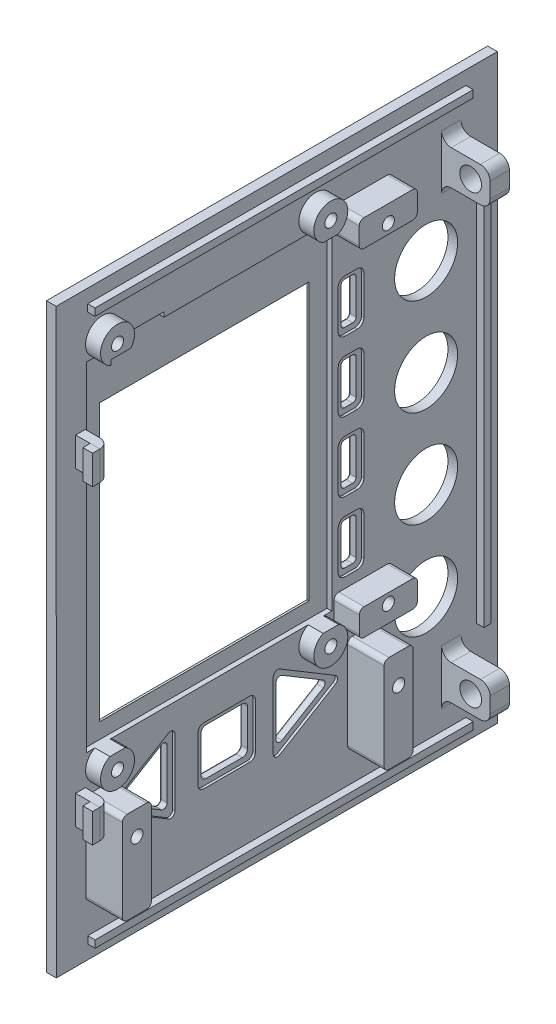
SolidWorks part; units mm, degrees
ref_plane "Front Plane" through (0, 0, 0) normal (0, 0, 1) x (1, 0, 0)
ref_plane "Top Plane" through (0, 0, 0) normal (0, 1, 0) x (1, 0, 0)
ref_plane "Right Plane" through (0, 0, 0) normal (1, 0, 0) x (0, 0, -1)
ref_plane "Plane2" through (-1175.048, -0.0877, 0) normal (-1, -0.0001, 0) x (0, 0, 1)
sketch "Sketch2" plane through (-1175.048, -0.0877, 0) normal (-1, -0.0001, 0) x (0, 0, 1)
  line L0 (-1289.195, -889.282) -> (-1289.195, -789.282) construction
  line L1 (-1204.195, -779.282) -> (-1295.195, -779.282)
  line L2 (-1204.195, -779.282) -> (-1204.195, -899.282)
  line L3 (-1204.195, -899.282) -> (-1295.195, -899.282)
  line L4 (-1295.195, -779.282) -> (-1295.195, -899.282)
  line L5 (-1289.195, -889.282) -> (-1287.685, -889.282) construction
  line L6 (-1289.195, -789.282) -> (-1287.685, -789.282) construction
  circle A0 centre (-1280.5, -869.282) radius 6.5
  circle A1 centre (-1280.5, -849.282) radius 6.5
  circle A2 centre (-1280.5, -829.282) radius 6.5
  circle A3 centre (-1280.5, -809.282) radius 6.5
  ellipse E0 centre (-1280.5, -869.282) end of major axis (-1280.4976, -868.632) minor radius 0.65 construction
  ellipse E1 centre (-1280.5, -849.282) end of major axis (-1280.4976, -848.632) minor radius 0.65 construction
  ellipse E2 centre (-1280.5, -829.282) end of major axis (-1280.4976, -828.632) minor radius 0.65 construction
  ellipse E3 centre (-1280.5, -809.282) end of major axis (-1280.4976, -808.632) minor radius 0.65 construction
  ellipse E4 centre (-1280.5, -869.282) end of major axis (-1280.4976, -868.632) minor radius 0.65
  ellipse E5 centre (-1280.5, -849.282) end of major axis (-1280.4976, -848.632) minor radius 0.65 construction
  ellipse E6 centre (-1280.5, -829.282) end of major axis (-1280.4976, -828.632) minor radius 0.65
  ellipse E7 centre (-1280.5, -809.282) end of major axis (-1280.4976, -808.632) minor radius 0.65
  dimension "D5" = 13
  dimension "D6" = 13
  dimension "D7" = 13
  dimension "D8" = 13
  dimension "D1" = 6
  dimension "D2" = 10
  dimension "D3" = 10
  dimension "D4" = 91
extrude "Boss-Extrude2" add sketch "Sketch2" along normal blind 2 contours L1 L4 L3 L2 A3 A2 A1 A0 region at (-1174.9854, -839.3697, -1248.1207)
sketch "Sketch3" plane through (-1177.048, -0.0879, 0) normal (-1, -0.0001, 0) x (0, 0, 1)
  line L12 (-1214.15, -858.982) -> (-1257.35, -858.982) construction
  line L13 (-1257.35, -858.982) -> (-1257.35, -802.002) construction
  line L14 (-1214.15, -802.002) -> (-1214.15, -858.982) construction
  line L15 (-1257.35, -802.002) -> (-1214.15, -802.002) construction
  line L16 (-1214.15, -858.982) -> (-1257.35, -858.982)
  line L17 (-1257.35, -858.982) -> (-1257.35, -802.002)
  line L18 (-1214.15, -802.002) -> (-1214.15, -858.982)
  line L19 (-1257.35, -802.002) -> (-1214.15, -802.002)
extrude "tft_cutout" cut sketch "Sketch3" against normal through all
sketch "tft_inset_cutout" plane through (-1175.048, -0.0877, 0) normal (1, 0.0001, 0) x (0, 0, -1)
  line L4 (1210.95, -792.861) -> (1210.95, -861.661) construction
  line L5 (1260.55, -792.861) -> (1210.95, -792.861) construction
  line L12 (1260.55, -861.661) -> (1260.55, -792.861) construction
  line L17 (1210.95, -861.661) -> (1260.55, -861.661) construction
  line L18 (1260.55, -861.661) -> (1260.55, -792.861) construction
  line L19 (1210.95, -861.661) -> (1260.55, -861.661) construction
  line L20 (1210.95, -792.861) -> (1210.95, -861.661) construction
  line L21 (1260.55, -792.861) -> (1210.95, -792.861) construction
  line L22 (1261.05, -792.361) -> (1210.45, -792.361)
  line L26 (1212.45, -792.861) -> (1226.45, -792.861)
  line L27 (1212.45, -792.861) -> (1212.45, -791.361)
  line L28 (1212.45, -791.361) -> (1226.45, -791.361)
  line L29 (1226.45, -792.861) -> (1226.45, -791.361)
  line L30 (1210.45, -792.361) -> (1210.45, -862.161)
  line L31 (1210.45, -862.161) -> (1261.05, -862.161)
  line L32 (1261.05, -862.161) -> (1261.05, -792.361)
  line M40 (1257.35, -858.982) -> (1214.15, -858.982)
  line M41 (1214.15, -858.982) -> (1214.15, -802.002)
  line M42 (1214.15, -802.002) -> (1257.35, -802.002)
  line M43 (1257.35, -802.002) -> (1257.35, -858.982)
  dimension "D3" = 1.5
  dimension "D4" = 0.5
  dimension "D1" = 14
  dimension "D2" = 1.5
extrude "Cut-Extrude2" cut sketch "tft_inset_cutout" against normal up to surface (1 mm away) contours L18 | L31 L32 L22 L29 L26 L27 L30 M43 M40 M41 M42 | L26 L29 L22 L27 | L22 L29 L28 L27 region at (-1174.9863, -827.3487, -1260.1879) region at (-1174.9889, -792.6987, -1219.45) region at (-1174.9889, -791.9487, -1219.45)
chamfer "Chamfer2" distance 1 angle 30 4 edges at (-1176.986, -830.5798, -1257.35) (-1176.9839, -859.0698, -1235.75) (-1176.986, -830.5798, -1214.15) (-1176.9882, -802.0898, -1235.75) first distance on face at (-1176.986, -830.5798, -1235.75)
sketch "Sketch6" plane through (-1175.048, -0.0877, 0) normal (1, 0.0001, 0) x (0, 0, -1)
  line L5 (1261.5, -864.9905) -> (1273.5, -864.9905)
  line L6 (1261.5, -864.9905) -> (1261.5, -859.4905)
  line L7 (1261.5, -859.4905) -> (1273.5, -859.4905)
  line L8 (1261.5, -864.9905) -> (1273.5, -864.9905)
  line L9 (1273.5, -864.9905) -> (1273.5, -789.9905)
  line L10 (1273.5, -789.9905) -> (1261.5, -789.9905)
  line L11 (1261.5, -789.9905) -> (1261.5, -864.9905)
  line L12 (1261.5, -864.9905) -> (1273.5, -864.9905) construction
  line L13 (1273.5, -864.9905) -> (1273.5, -789.9905) construction
  line L14 (1273.5, -789.9905) -> (1261.5, -789.9905) construction
  line L15 (1261.5, -789.9905) -> (1261.5, -864.9905) construction
  line L16 (1273.5, -864.9905) -> (1273.5, -859.4905)
  line L17 (1261.5, -789.9905) -> (1273.5, -789.9905)
  line L18 (1261.5, -789.9905) -> (1261.5, -795.4905)
  line L19 (1261.5, -795.4905) -> (1273.5, -795.4905)
  line L20 (1273.5, -789.9905) -> (1273.5, -795.4905)
  circle A0 centre (1267.5, -861.4905) radius 1.25 construction
  circle A1 centre (1267.5, -861.4905) radius 1.25 construction
  circle A2 centre (1267.5, -861.4905) radius 1.25
  circle A3 centre (1267.5, -793.4905) radius 1.25 construction
  circle A4 centre (1267.5, -793.4905) radius 1.25 construction
  circle A5 centre (1267.5, -793.4905) radius 1.25
  dimension "D2" = 2.5
  dimension "D4" = 2.5
  dimension "D3" = 2
  dimension "D5" = 2
extrude "menu_standoffs" add sketch "Sketch6" along normal up to surface (5.203 mm away)
fillet "Fillet1" radius 1 8 edges at (-1172.3871, -795.578, -1261.5) (-1172.3871, -795.578, -1273.5) (-1172.3875, -790.078, -1273.5) (-1172.3875, -790.078, -1261.5) (-1172.3824, -859.578, -1273.5) (-1172.3824, -859.578, -1261.5) (-1172.382, -865.078, -1261.5) (-1172.382, -865.078, -1273.5)
sketch "Sketch7" plane through (-1169.845, -0.0873, 0) normal (1, 0.0001, 0) x (0, 0, -1)
  circle A0 centre (1267.5, -861.4905) radius 1.25 construction
  circle A1 centre (1267.5, -793.4905) radius 1.25 construction
  circle A2 centre (1267.5, -861.4905) radius 1.25
  circle A3 centre (1267.5, -793.4905) radius 1.25
extrude "menu_standoff_holes" [suppressed] cut sketch "Sketch7" against normal blind 5 contours A2
sketch "Sketch8" plane through (-1175.048, -0.0877, 0) normal (1, 0.0001, 0) x (0, 0, -1)
  circle A0 centre (1213.75, -865.282) radius 1.55 construction
  circle A1 centre (1257.75, -865.282) radius 1.55 construction
  circle A2 centre (1257.75, -789.202) radius 1.55 construction
  circle A3 centre (1213.75, -789.2023) radius 1.55 construction
  circle A4 centre (1213.75, -865.282) radius 1.55 construction
  circle A5 centre (1257.75, -865.282) radius 1.55 construction
  circle A6 centre (1257.75, -789.202) radius 1.55 construction
  circle A7 centre (1213.75, -789.2023) radius 1.55 construction
  circle A8 centre (1213.75, -789.2023) radius 3.5
  circle A9 centre (1257.75, -789.202) radius 3.5
  circle A10 centre (1257.75, -865.282) radius 3.5
  circle A11 centre (1213.75, -865.282) radius 3.5
  circle A12 centre (1213.75, -789.2023) radius 1.25
  circle A13 centre (1213.75, -865.282) radius 1.25
  circle A14 centre (1257.75, -865.282) radius 1.25
  circle A15 centre (1257.75, -789.202) radius 1.25
  dimension "D2" = 2.5
  dimension "D1" = 7
extrude "TFT_standoffs" add sketch "Sketch8" along normal up to surface (3.09 mm away)
sketch "Sketch9" plane through (-1175.048, -0.0877, 0) normal (1, 0.0001, 0) x (0, 0, -1)
  circle A0 centre (1213.75, -789.2023) radius 1.25 construction
  circle A1 centre (1213.75, -865.282) radius 1.25 construction
  circle A2 centre (1257.75, -865.282) radius 1.25 construction
  circle A3 centre (1257.75, -789.202) radius 1.25 construction
  circle A4 centre (1213.75, -789.2023) radius 1.25
  circle A5 centre (1213.75, -865.282) radius 1.25
  circle A6 centre (1257.75, -865.282) radius 1.25
  circle A7 centre (1257.75, -789.202) radius 1.25
extrude "TFT_standoff_holes" cut sketch "Sketch9" against normal offset from surface (1 mm away) 1 up to face at (-1176.986, -830.5798, -1235.75)
extrude "Cut-Extrude5" cut sketch "Sketch5<3>" along normal through all contours L31 L32 L22 L29 L26 L27 L30 M43 M40 M41 M42 | L22 L29 L28 L27 | L26 L29 L22 L27 region at (-1174.9863, -827.3487, -1260.1879) region at (-1174.9889, -792.6987, -1219.45) region at (-1174.9889, -791.9487, -1219.45)
sketch "Sketch5<3>" plane through (-1175.048, -0.0877, 0) normal (1, 0.0001, 0) x (0, 0, -1) same geometry as "tft_inset_cutout"
sketch "Sketch10" plane through (-1175.048, -0.0877, 0) normal (1, 0.0001, 0) x (0, 0, -1)
  line L0 (1267.2535, -804.997) -> (1267.2535, -812.997) construction
  line L1 (1266.2535, -813.997) -> (1263.7535, -813.997) construction
  line L2 (1262.7535, -812.997) -> (1262.7535, -804.997) construction
  line L3 (1263.7535, -803.997) -> (1266.2535, -803.997) construction
  line L4 (1267.2535, -804.997) -> (1267.2535, -812.997) construction
  line L5 (1266.2535, -813.997) -> (1263.7535, -813.997) construction
  line L6 (1262.7535, -812.997) -> (1262.7535, -804.997) construction
  line L7 (1263.7535, -803.997) -> (1266.2535, -803.997) construction
  line L8 (1267.6535, -804.997) -> (1267.6535, -812.997)
  line L9 (1266.2535, -814.397) -> (1263.7535, -814.397)
  line L10 (1262.3535, -812.997) -> (1262.3535, -804.997)
  line L11 (1263.7535, -803.597) -> (1266.2535, -803.597)
  line L12 (1267.6535, -819.327) -> (1267.6535, -827.327)
  line L13 (1266.2535, -828.727) -> (1263.7535, -828.727)
  line L14 (1262.3535, -827.327) -> (1262.3535, -819.327)
  line L15 (1263.7535, -817.927) -> (1266.2535, -817.927)
  line L16 (1267.2535, -819.327) -> (1267.2535, -827.327) construction
  line L17 (1266.2535, -828.327) -> (1263.7535, -828.327) construction
  line L18 (1262.7535, -827.327) -> (1262.7535, -819.327) construction
  line L19 (1263.7535, -818.327) -> (1266.2535, -818.327) construction
  line L20 (1267.6535, -833.657) -> (1267.6535, -841.657)
  line L21 (1266.2535, -843.057) -> (1263.7535, -843.057)
  line L22 (1262.3535, -841.657) -> (1262.3535, -833.657)
  line L23 (1263.7535, -832.257) -> (1266.2535, -832.257)
  line L24 (1267.2535, -833.657) -> (1267.2535, -841.657) construction
  line L25 (1266.2535, -842.657) -> (1263.7535, -842.657) construction
  line L26 (1262.7535, -841.657) -> (1262.7535, -833.657) construction
  line L27 (1263.7535, -832.657) -> (1266.2535, -832.657) construction
  line L28 (1267.6535, -847.987) -> (1267.6535, -855.987)
  line L29 (1266.2535, -857.387) -> (1263.7535, -857.387)
  line L30 (1262.3535, -855.987) -> (1262.3535, -847.987)
  line L31 (1263.7535, -846.587) -> (1266.2535, -846.587)
  line L32 (1267.2535, -847.987) -> (1267.2535, -855.987) construction
  line L33 (1266.2535, -856.987) -> (1263.7535, -856.987) construction
  line L34 (1262.7535, -855.987) -> (1262.7535, -847.987) construction
  line L35 (1263.7535, -846.987) -> (1266.2535, -846.987) construction
  arc A0 (1267.2535, -804.997) -> (1266.2535, -803.997) centre (1266.2535, -804.997) ccw construction
  arc A1 (1266.2535, -813.997) -> (1267.2535, -812.997) centre (1266.2535, -812.997) ccw construction
  arc A2 (1262.7535, -812.997) -> (1263.7535, -813.997) centre (1263.7535, -812.997) ccw construction
  arc A3 (1263.7535, -803.997) -> (1262.7535, -804.997) centre (1263.7535, -804.997) ccw construction
  arc A4 (1267.2535, -804.997) -> (1266.2535, -803.997) centre (1266.2535, -804.997) ccw construction
  arc A5 (1266.2535, -813.997) -> (1267.2535, -812.997) centre (1266.2535, -812.997) ccw construction
  arc A6 (1262.7535, -812.997) -> (1263.7535, -813.997) centre (1263.7535, -812.997) ccw construction
  arc A7 (1263.7535, -803.997) -> (1262.7535, -804.997) centre (1263.7535, -804.997) ccw construction
  arc A8 (1266.2535, -814.397) -> (1267.6535, -812.997) centre (1266.2535, -812.997) ccw
  arc A9 (1262.3535, -812.997) -> (1263.7535, -814.397) centre (1263.7535, -812.997) ccw
  arc A10 (1263.7535, -803.597) -> (1262.3535, -804.997) centre (1263.7535, -804.997) ccw
  arc A11 (1267.6535, -804.997) -> (1266.2535, -803.597) centre (1266.2535, -804.997) ccw
  arc A12 (1266.2535, -828.727) -> (1267.6535, -827.327) centre (1266.2535, -827.327) ccw
  arc A13 (1262.3535, -827.327) -> (1263.7535, -828.727) centre (1263.7535, -827.327) ccw
  arc A14 (1263.7535, -817.927) -> (1262.3535, -819.327) centre (1263.7535, -819.327) ccw
  arc A15 (1267.6535, -819.327) -> (1266.2535, -817.927) centre (1266.2535, -819.327) ccw
  arc A16 (1267.2535, -819.327) -> (1266.2535, -818.327) centre (1266.2535, -819.327) ccw construction
  arc A17 (1266.2535, -828.327) -> (1267.2535, -827.327) centre (1266.2535, -827.327) ccw construction
  arc A18 (1262.7535, -827.327) -> (1263.7535, -828.327) centre (1263.7535, -827.327) ccw construction
  arc A19 (1263.7535, -818.327) -> (1262.7535, -819.327) centre (1263.7535, -819.327) ccw construction
  arc A20 (1266.2535, -843.057) -> (1267.6535, -841.657) centre (1266.2535, -841.657) ccw
  arc A21 (1262.3535, -841.657) -> (1263.7535, -843.057) centre (1263.7535, -841.657) ccw
  arc A22 (1263.7535, -832.257) -> (1262.3535, -833.657) centre (1263.7535, -833.657) ccw
  arc A23 (1267.6535, -833.657) -> (1266.2535, -832.257) centre (1266.2535, -833.657) ccw
  arc A24 (1267.2535, -833.657) -> (1266.2535, -832.657) centre (1266.2535, -833.657) ccw construction
  arc A25 (1266.2535, -842.657) -> (1267.2535, -841.657) centre (1266.2535, -841.657) ccw construction
  arc A26 (1262.7535, -841.657) -> (1263.7535, -842.657) centre (1263.7535, -841.657) ccw construction
  arc A27 (1263.7535, -832.657) -> (1262.7535, -833.657) centre (1263.7535, -833.657) ccw construction
  arc A28 (1266.2535, -857.387) -> (1267.6535, -855.987) centre (1266.2535, -855.987) ccw
  arc A29 (1262.3535, -855.987) -> (1263.7535, -857.387) centre (1263.7535, -855.987) ccw
  arc A30 (1263.7535, -846.587) -> (1262.3535, -847.987) centre (1263.7535, -847.987) ccw
  arc A31 (1267.6535, -847.987) -> (1266.2535, -846.587) centre (1266.2535, -847.987) ccw
  arc A32 (1267.2535, -847.987) -> (1266.2535, -846.987) centre (1266.2535, -847.987) ccw construction
  arc A33 (1266.2535, -856.987) -> (1267.2535, -855.987) centre (1266.2535, -855.987) ccw construction
  arc A34 (1262.7535, -855.987) -> (1263.7535, -856.987) centre (1263.7535, -855.987) ccw construction
  arc A35 (1263.7535, -846.987) -> (1262.7535, -847.987) centre (1263.7535, -847.987) ccw construction
  dimension "D1" = 0.4
  dimension "D2" = 4
extrude "menu_panel_inset" cut sketch "Sketch10" against normal offset from surface 1.5 and the other way through all up to face at (-1176.986, -830.5798, -1235.75)
sketch "Sketch11" plane through (-1177.048, -0.0879, 0) normal (-1, -0.0001, 0) x (0, 0, 1)
  line L0 (-1265.8535, -812.997) -> (-1264.1535, -812.997) construction
  line L1 (-1266.2535, -805.397) -> (-1266.2535, -812.597) construction
  line L2 (-1265.8535, -804.997) -> (-1264.1535, -804.997) construction
  line L3 (-1263.7535, -805.397) -> (-1263.7535, -812.597) construction
  line L4 (-1265.8535, -812.997) -> (-1264.1535, -812.997) construction
  line L5 (-1266.2535, -805.397) -> (-1266.2535, -812.597) construction
  line L6 (-1265.8535, -804.997) -> (-1264.1535, -804.997) construction
  line L7 (-1263.7535, -805.397) -> (-1263.7535, -812.597) construction
  line L8 (-1263.4535, -805.397) -> (-1263.4535, -812.597)
  line L9 (-1265.8535, -813.297) -> (-1264.1535, -813.297)
  line L10 (-1266.5535, -805.397) -> (-1266.5535, -812.597)
  line L11 (-1265.8535, -804.697) -> (-1264.1535, -804.697)
  line L12 (-1263.4535, -819.727) -> (-1263.4535, -826.927)
  line L13 (-1265.8535, -827.627) -> (-1264.1535, -827.627)
  line L14 (-1266.5535, -819.727) -> (-1266.5535, -826.927)
  line L15 (-1265.8535, -819.027) -> (-1264.1535, -819.027)
  line L16 (-1265.8535, -827.327) -> (-1264.1535, -827.327) construction
  line L17 (-1266.2535, -819.727) -> (-1266.2535, -826.927) construction
  line L18 (-1265.8535, -819.327) -> (-1264.1535, -819.327) construction
  line L19 (-1263.7535, -819.727) -> (-1263.7535, -826.927) construction
  line L20 (-1263.4535, -834.057) -> (-1263.4535, -841.257)
  line L21 (-1265.8535, -841.957) -> (-1264.1535, -841.957)
  line L22 (-1266.5535, -834.057) -> (-1266.5535, -841.257)
  line L23 (-1265.8535, -833.357) -> (-1264.1535, -833.357)
  line L24 (-1265.8535, -841.657) -> (-1264.1535, -841.657) construction
  line L25 (-1266.2535, -834.057) -> (-1266.2535, -841.257) construction
  line L26 (-1265.8535, -833.657) -> (-1264.1535, -833.657) construction
  line L27 (-1263.7535, -834.057) -> (-1263.7535, -841.257) construction
  line L28 (-1263.4535, -848.387) -> (-1263.4535, -855.587)
  line L29 (-1265.8535, -856.287) -> (-1264.1535, -856.287)
  line L30 (-1266.5535, -848.387) -> (-1266.5535, -855.587)
  line L31 (-1265.8535, -847.687) -> (-1264.1535, -847.687)
  line L32 (-1265.8535, -855.987) -> (-1264.1535, -855.987) construction
  line L33 (-1266.2535, -848.387) -> (-1266.2535, -855.587) construction
  line L34 (-1265.8535, -847.987) -> (-1264.1535, -847.987) construction
  line L35 (-1263.7535, -848.387) -> (-1263.7535, -855.587) construction
  arc A0 (-1264.1535, -812.997) -> (-1263.7535, -812.597) centre (-1264.1535, -812.597) ccw construction
  arc A1 (-1266.2535, -812.597) -> (-1265.8535, -812.997) centre (-1265.8535, -812.597) ccw construction
  arc A2 (-1265.8535, -804.997) -> (-1266.2535, -805.397) centre (-1265.8535, -805.397) ccw construction
  arc A3 (-1263.7535, -805.397) -> (-1264.1535, -804.997) centre (-1264.1535, -805.397) ccw construction
  arc A4 (-1264.1535, -812.997) -> (-1263.7535, -812.597) centre (-1264.1535, -812.597) ccw construction
  arc A5 (-1266.2535, -812.597) -> (-1265.8535, -812.997) centre (-1265.8535, -812.597) ccw construction
  arc A6 (-1265.8535, -804.997) -> (-1266.2535, -805.397) centre (-1265.8535, -805.397) ccw construction
  arc A7 (-1263.7535, -805.397) -> (-1264.1535, -804.997) centre (-1264.1535, -805.397) ccw construction
  arc A8 (-1264.1535, -813.297) -> (-1263.4535, -812.597) centre (-1264.1535, -812.597) ccw
  arc A9 (-1266.5535, -812.597) -> (-1265.8535, -813.297) centre (-1265.8535, -812.597) ccw
  arc A10 (-1265.8535, -804.697) -> (-1266.5535, -805.397) centre (-1265.8535, -805.397) ccw
  arc A11 (-1263.4535, -805.397) -> (-1264.1535, -804.697) centre (-1264.1535, -805.397) ccw
  arc A12 (-1264.1535, -827.627) -> (-1263.4535, -826.927) centre (-1264.1535, -826.927) ccw
  arc A13 (-1266.5535, -826.927) -> (-1265.8535, -827.627) centre (-1265.8535, -826.927) ccw
  arc A14 (-1265.8535, -819.027) -> (-1266.5535, -819.727) centre (-1265.8535, -819.727) ccw
  arc A15 (-1263.4535, -819.727) -> (-1264.1535, -819.027) centre (-1264.1535, -819.727) ccw
  arc A16 (-1264.1535, -827.327) -> (-1263.7535, -826.927) centre (-1264.1535, -826.927) ccw construction
  arc A17 (-1266.2535, -826.927) -> (-1265.8535, -827.327) centre (-1265.8535, -826.927) ccw construction
  arc A18 (-1265.8535, -819.327) -> (-1266.2535, -819.727) centre (-1265.8535, -819.727) ccw construction
  arc A19 (-1263.7535, -819.727) -> (-1264.1535, -819.327) centre (-1264.1535, -819.727) ccw construction
  arc A20 (-1264.1535, -841.957) -> (-1263.4535, -841.257) centre (-1264.1535, -841.257) ccw
  arc A21 (-1266.5535, -841.257) -> (-1265.8535, -841.957) centre (-1265.8535, -841.257) ccw
  arc A22 (-1265.8535, -833.357) -> (-1266.5535, -834.057) centre (-1265.8535, -834.057) ccw
  arc A23 (-1263.4535, -834.057) -> (-1264.1535, -833.357) centre (-1264.1535, -834.057) ccw
  arc A24 (-1264.1535, -841.657) -> (-1263.7535, -841.257) centre (-1264.1535, -841.257) ccw construction
  arc A25 (-1266.2535, -841.257) -> (-1265.8535, -841.657) centre (-1265.8535, -841.257) ccw construction
  arc A26 (-1265.8535, -833.657) -> (-1266.2535, -834.057) centre (-1265.8535, -834.057) ccw construction
  arc A27 (-1263.7535, -834.057) -> (-1264.1535, -833.657) centre (-1264.1535, -834.057) ccw construction
  arc A28 (-1264.1535, -856.287) -> (-1263.4535, -855.587) centre (-1264.1535, -855.587) ccw
  arc A29 (-1266.5535, -855.587) -> (-1265.8535, -856.287) centre (-1265.8535, -855.587) ccw
  arc A30 (-1265.8535, -847.687) -> (-1266.5535, -848.387) centre (-1265.8535, -848.387) ccw
  arc A31 (-1263.4535, -848.387) -> (-1264.1535, -847.687) centre (-1264.1535, -848.387) ccw
  arc A32 (-1264.1535, -855.987) -> (-1263.7535, -855.587) centre (-1264.1535, -855.587) ccw construction
  arc A33 (-1266.2535, -855.587) -> (-1265.8535, -855.987) centre (-1265.8535, -855.587) ccw construction
  arc A34 (-1265.8535, -847.987) -> (-1266.2535, -848.387) centre (-1265.8535, -848.387) ccw construction
  arc A35 (-1263.7535, -848.387) -> (-1264.1535, -847.987) centre (-1264.1535, -848.387) ccw construction
  dimension "D1" = 0.3
  dimension "D2" = 4
extrude "menu_panel_cutout" cut sketch "Sketch11" against normal through all
fillet "Fillet2" radius 0.25 32 edges at (-1176.9876, -809.0848, -1263.4535) (-1176.9873, -813.1798, -1263.6586) (-1176.9873, -813.3848, -1265.0035) (-1176.9873, -813.1798, -1266.3485) (-1176.9876, -809.0848, -1266.5535) (-1176.9879, -804.9899, -1266.3485) (-1176.988, -804.7848, -1265.0035) (-1176.9862, -827.7148, -1265.0035) (-1176.9863, -827.5098, -1266.3485) (-1176.9866, -823.4148, -1266.5535) (-1176.9869, -819.3199, -1266.3485) (-1176.9869, -819.1148, -1265.0035) (-1176.9869, -819.3199, -1263.6586) (-1176.9866, -823.4148, -1263.4535) (-1176.9852, -842.0448, -1265.0035) (-1176.9852, -841.8398, -1266.3485) (-1176.9855, -837.7448, -1266.5535) (-1176.9858, -833.6499, -1266.3485) (-1176.9858, -833.4448, -1265.0035) (-1176.9858, -833.6499, -1263.6586) (-1176.9855, -837.7448, -1263.4535) (-1176.9844, -852.0748, -1263.4535) (-1176.9841, -856.1698, -1263.6586) (-1176.9841, -856.3748, -1265.0035) (-1176.9841, -856.1698, -1266.3485) (-1176.9844, -852.0748, -1266.5535) (-1176.9847, -847.9799, -1266.3485) (-1176.9847, -847.7748, -1265.0035) (-1176.9879, -804.9899, -1263.6586) (-1176.9863, -827.5098, -1263.6586) (-1176.9852, -841.8398, -1263.6586) (-1176.9847, -847.9799, -1263.6586)
sketch "Sketch12" plane through (-1175.048, -0.0877, 0) normal (1, 0.0001, 0) x (0, 0, -1)
  line L0 (1270.2797, -888.782) -> (1210.2797, -888.782) construction
  line L1 (1270.2797, -868.782) -> (1264.2797, -868.782)
  line L2 (1270.2797, -868.782) -> (1270.2797, -888.782)
  line L3 (1270.2797, -888.782) -> (1264.2797, -888.782)
  line L4 (1264.2797, -868.782) -> (1264.2797, -888.782)
  line L6 (1210.2797, -888.782) -> (1216.2797, -888.782)
  line L7 (1210.2797, -888.782) -> (1210.2797, -869.782)
  line L8 (1210.2797, -869.782) -> (1216.2797, -869.782)
  line L9 (1216.2797, -888.782) -> (1216.2797, -869.782)
  line L10 (1210.2797, -868.782) -> (1270.2797, -868.782) construction
  circle A0 centre (1267.2797, -874.782) radius 1.25
  circle A1 centre (1213.2797, -874.782) radius 1.25
  dimension "D1" = 6
  dimension "D2" = 2.5
  dimension "D4" = 2.5
  dimension "D3" = 6
  dimension "D5" = 1
extrude "selector_standoffs" add sketch "Sketch12" along normal up to surface (7.55 mm away) contours L6 L9 L8 L7 A1 | L1 L4 L3 L2 A0 region at (-1174.9824, -879.0403, -1267.2797) region at (-1174.9824, -879.5722, -1213.2797)
fillet "Fillet3" radius 1 8 edges at (-1171.2067, -888.8694, -1270.2797) (-1171.2082, -868.8694, -1270.2797) (-1171.2082, -868.8694, -1264.2797) (-1171.2067, -888.8694, -1264.2797) (-1171.2067, -888.8694, -1216.2797) (-1171.2067, -888.8694, -1210.2797) (-1171.2081, -869.8694, -1210.2797) (-1171.2081, -869.8694, -1216.2797)
sketch "Sketch13" plane through (-1175.048, -0.0877, 0) normal (1, 0.0001, 0) x (0, 0, -1)
  line L0 (1218.0014, -875.2178) -> (1226.5296, -880.3347) construction
  line L1 (1227.2868, -879.906) -> (1227.2868, -869.6722) construction
  line L2 (1226.5296, -869.2434) -> (1218.0014, -874.3603) construction
  line L3 (1234.85, -871.0391) -> (1234.85, -878.5391) construction
  line L4 (1235.6, -879.2891) -> (1243.1, -879.2891) construction
  line L5 (1243.1, -870.2891) -> (1235.6, -870.2891) construction
  line L6 (1243.85, -878.5391) -> (1243.85, -871.0391) construction
  line L7 (1259.6354, -874.3603) -> (1251.1072, -869.2434) construction
  line L8 (1250.35, -869.6722) -> (1250.35, -879.906) construction
  line L9 (1251.1072, -880.3347) -> (1259.6354, -875.2178) construction
  line L10 (1218.0014, -875.2178) -> (1226.5296, -880.3347) construction
  line L11 (1227.2868, -879.906) -> (1227.2868, -869.6722) construction
  line L12 (1226.5296, -869.2434) -> (1218.0014, -874.3603) construction
  line L13 (1234.85, -871.0391) -> (1234.85, -878.5391) construction
  line L14 (1235.6, -879.2891) -> (1243.1, -879.2891) construction
  line L15 (1243.1, -870.2891) -> (1235.6, -870.2891) construction
  line L16 (1243.85, -878.5391) -> (1243.85, -871.0391) construction
  line L17 (1259.6354, -874.3603) -> (1251.1072, -869.2434) construction
  line L18 (1250.35, -869.6722) -> (1250.35, -879.906) construction
  line L19 (1251.1072, -880.3347) -> (1259.6354, -875.2178) construction
  line L20 (1217.847, -875.4751) -> (1226.3752, -880.592)
  line L21 (1227.5868, -879.906) -> (1227.5868, -869.6722)
  line L22 (1226.3752, -868.9862) -> (1217.847, -874.1031)
  line L23 (1234.55, -871.0391) -> (1234.55, -878.5391)
  line L24 (1235.6, -879.5891) -> (1243.1, -879.5891)
  line L25 (1244.15, -878.5391) -> (1244.15, -871.0391)
  line L26 (1243.1, -869.9891) -> (1235.6, -869.9891)
  line L27 (1259.7898, -874.1031) -> (1251.2616, -868.9862)
  line L28 (1250.05, -869.6722) -> (1250.05, -879.906)
  line L29 (1251.2616, -880.592) -> (1259.7898, -875.4751)
  arc A0 (1218.0014, -874.3603) -> (1218.0014, -875.2178) centre (1218.2586, -874.7891) ccw construction
  arc A1 (1226.5296, -880.3347) -> (1227.2868, -879.906) centre (1226.7868, -879.906) ccw construction
  arc A2 (1227.2868, -869.6722) -> (1226.5296, -869.2434) centre (1226.7868, -869.6722) ccw construction
  arc A3 (1235.6, -870.2891) -> (1234.85, -871.0391) centre (1235.6, -871.0391) ccw construction
  arc A4 (1234.85, -878.5391) -> (1235.6, -879.2891) centre (1235.6, -878.5391) ccw construction
  arc A5 (1243.1, -879.2891) -> (1243.85, -878.5391) centre (1243.1, -878.5391) ccw construction
  arc A6 (1243.85, -871.0391) -> (1243.1, -870.2891) centre (1243.1, -871.0391) ccw construction
  arc A7 (1259.6354, -875.2178) -> (1259.6354, -874.3603) centre (1259.3782, -874.7891) ccw construction
  arc A8 (1251.1072, -869.2434) -> (1250.35, -869.6722) centre (1250.85, -869.6722) ccw construction
  arc A9 (1250.35, -879.906) -> (1251.1072, -880.3347) centre (1250.85, -879.906) ccw construction
  arc A10 (1218.0014, -874.3603) -> (1218.0014, -875.2178) centre (1218.2586, -874.7891) ccw construction
  arc A11 (1226.5296, -880.3347) -> (1227.2868, -879.906) centre (1226.7868, -879.906) ccw construction
  arc A12 (1227.2868, -869.6722) -> (1226.5296, -869.2434) centre (1226.7868, -869.6722) ccw construction
  arc A13 (1235.6, -870.2891) -> (1234.85, -871.0391) centre (1235.6, -871.0391) ccw construction
  arc A14 (1234.85, -878.5391) -> (1235.6, -879.2891) centre (1235.6, -878.5391) ccw construction
  arc A15 (1243.1, -879.2891) -> (1243.85, -878.5391) centre (1243.1, -878.5391) ccw construction
  arc A16 (1243.85, -871.0391) -> (1243.1, -870.2891) centre (1243.1, -871.0391) ccw construction
  arc A17 (1259.6354, -875.2178) -> (1259.6354, -874.3603) centre (1259.3782, -874.7891) ccw construction
  arc A18 (1251.1072, -869.2434) -> (1250.35, -869.6722) centre (1250.85, -869.6722) ccw construction
  arc A19 (1250.35, -879.906) -> (1251.1072, -880.3347) centre (1250.85, -879.906) ccw construction
  arc A20 (1226.3752, -880.592) -> (1227.5868, -879.906) centre (1226.7868, -879.906) ccw
  arc A21 (1227.5868, -869.6722) -> (1226.3752, -868.9862) centre (1226.7868, -869.6722) ccw
  arc A22 (1217.847, -874.1031) -> (1217.847, -875.4751) centre (1218.2586, -874.7891) ccw
  arc A23 (1234.55, -878.5391) -> (1235.6, -879.5891) centre (1235.6, -878.5391) ccw
  arc A24 (1243.1, -879.5891) -> (1244.15, -878.5391) centre (1243.1, -878.5391) ccw
  arc A25 (1244.15, -871.0391) -> (1243.1, -869.9891) centre (1243.1, -871.0391) ccw
  arc A26 (1235.6, -869.9891) -> (1234.55, -871.0391) centre (1235.6, -871.0391) ccw
  arc A27 (1251.2616, -868.9862) -> (1250.05, -869.6722) centre (1250.85, -869.6722) ccw
  arc A28 (1250.05, -879.906) -> (1251.2616, -880.592) centre (1250.85, -879.906) ccw
  arc A29 (1259.7898, -875.4751) -> (1259.7898, -874.1031) centre (1259.3782, -874.7891) ccw
  dimension "D1" = 0.3
  dimension "D2" = 0.3
  dimension "D3" = 0.3
extrude "selector_cutout" cut sketch "Sketch13" against normal through all
fillet "Fillet4" radius 0.25 20 edges at (-1176.9824, -879.6769, -1239.35) (-1176.9824, -879.3694, -1234.8575) (-1176.9827, -874.8769, -1234.55) (-1176.9831, -870.3845, -1234.8575) (-1176.9831, -870.0769, -1239.35) (-1176.9831, -870.3845, -1243.8424) (-1176.9827, -874.8769, -1244.15) (-1176.9832, -869.0639, -1250.4558) (-1176.983, -871.6325, -1255.5257) (-1176.9827, -874.8769, -1260.1782) (-1176.9825, -878.1214, -1255.5257) (-1176.9823, -880.69, -1250.4558) (-1176.9824, -879.3694, -1243.8424) (-1176.9827, -874.8769, -1250.05) (-1176.9825, -878.1214, -1222.1111) (-1176.9827, -874.8769, -1217.4586) (-1176.983, -871.6325, -1222.1111) (-1176.9832, -869.0639, -1227.181) (-1176.9827, -874.8769, -1227.5868) (-1176.9823, -880.69, -1227.181)
sketch "Sketch17" plane through (-1175.048, -0.0877, 0) normal (1, 0.0001, 0) x (0, 0, -1)
  line L18 (1220.3082, -871.8101) -> (1216.0577, -874.3603) construction
  line L19 (1216.0577, -875.2178) -> (1220.3082, -877.7681) construction
  line L20 (1220.1868, -877.5537) -> (1220.1868, -872.0244) construction
  line L21 (1228.2868, -881.6722) -> (1228.2868, -867.906) construction
  line L22 (1227.5296, -867.4772) -> (1220.4505, -871.7247) construction
  line L23 (1220.5791, -871.6891) -> (1226.1368, -871.6891) construction
  line L24 (1226.3868, -871.9391) -> (1226.3868, -877.6391) construction
  line L25 (1226.1368, -877.8891) -> (1220.5791, -877.8891) construction
  line L26 (1220.4505, -877.8535) -> (1227.5296, -882.1009) construction
  line L27 (1220.3082, -871.8101) -> (1216.0577, -874.3603) construction
  line L28 (1216.0577, -875.2178) -> (1220.3082, -877.7681) construction
  line L29 (1220.1868, -877.5537) -> (1220.1868, -872.0244) construction
  line L30 (1228.2868, -881.6722) -> (1228.2868, -867.906) construction
  line L31 (1257.3286, -877.7681) -> (1261.5791, -875.2178) construction
  line L32 (1261.5791, -874.3603) -> (1257.3286, -871.8101) construction
  line L33 (1257.45, -872.0244) -> (1257.45, -877.5537) construction
  line L34 (1249.35, -867.906) -> (1249.35, -881.6722) construction
  line L35 (1250.1072, -882.1009) -> (1257.1863, -877.8535) construction
  line L36 (1257.0577, -877.8891) -> (1251.5, -877.8891) construction
  line L37 (1251.25, -877.6391) -> (1251.25, -871.9391) construction
  line L38 (1251.5, -871.6891) -> (1257.0577, -871.6891) construction
  line L39 (1257.1863, -871.7247) -> (1250.1072, -867.4772) construction
  line L40 (1233.85, -870.0391) -> (1233.85, -879.5391) construction
  line L41 (1234.6, -880.2891) -> (1244.1, -880.2891) construction
  line L42 (1244.85, -879.5391) -> (1244.85, -870.0391) construction
  line L43 (1244.1, -869.2891) -> (1234.6, -869.2891) construction
  line L44 (1257.3286, -877.7681) -> (1261.5791, -875.2178) construction
  line L45 (1261.5791, -874.3603) -> (1257.3286, -871.8101) construction
  line L46 (1257.45, -872.0244) -> (1257.45, -877.5537) construction
  line L47 (1249.35, -867.906) -> (1249.35, -881.6722) construction
  line L48 (1250.1072, -882.1009) -> (1257.1863, -877.8535) construction
  line L49 (1257.0577, -877.8891) -> (1251.5, -877.8891) construction
  line L50 (1251.25, -877.6391) -> (1251.25, -871.9391) construction
  line L51 (1251.5, -871.6891) -> (1257.0577, -871.6891) construction
  line L52 (1257.1863, -871.7247) -> (1250.1072, -867.4772) construction
  line L53 (1233.85, -870.0391) -> (1233.85, -879.5391) construction
  line L54 (1234.6, -880.2891) -> (1244.1, -880.2891) construction
  line L55 (1244.85, -879.5391) -> (1244.85, -870.0391) construction
  line L56 (1244.1, -869.2891) -> (1234.6, -869.2891) construction
  line L57 (1257.1863, -877.8535) -> (1257.3286, -877.7681)
  line L58 (1257.3286, -871.8101) -> (1257.1863, -871.7247)
  line L59 (1227.5296, -867.4772) -> (1220.4505, -871.7247) construction
  line L60 (1220.5791, -871.6891) -> (1226.1368, -871.6891) construction
  line L61 (1226.3868, -871.9391) -> (1226.3868, -877.6391) construction
  line L62 (1226.1368, -877.8891) -> (1220.5791, -877.8891) construction
  line L63 (1220.4505, -877.8535) -> (1227.5296, -882.1009) construction
  line L64 (1220.3082, -871.8101) -> (1220.4505, -871.7247)
  line L65 (1220.4505, -877.8535) -> (1220.3082, -877.7681)
  line L66 (1257.3921, -878.1965) -> (1257.5344, -878.1111)
  line L67 (1257.5344, -871.4671) -> (1257.3921, -871.3817)
  line L68 (1220.514, -872.1531) -> (1220.6563, -872.0677)
  line L69 (1220.6563, -877.5105) -> (1220.514, -877.4251)
  line L70 (1220.1024, -871.4671) -> (1215.8519, -874.0173)
  line L71 (1215.8519, -875.5608) -> (1220.1024, -878.1111)
  line L72 (1220.5868, -877.4811) -> (1220.5868, -872.0971)
  line L73 (1220.2447, -878.1965) -> (1227.3238, -882.4439)
  line L74 (1228.6868, -881.6722) -> (1228.6868, -867.906)
  line L75 (1227.3238, -867.1342) -> (1220.2447, -871.3817)
  line L76 (1257.5344, -878.1111) -> (1261.7849, -875.5608)
  line L77 (1261.7849, -874.0173) -> (1257.5344, -871.4671)
  line L78 (1257.05, -872.0971) -> (1257.05, -877.4811)
  line L79 (1257.3921, -871.3817) -> (1250.313, -867.1342)
  line L80 (1248.95, -867.906) -> (1248.95, -881.6722)
  line L81 (1250.313, -882.4439) -> (1257.3921, -878.1965)
  line L82 (1257.0213, -877.4891) -> (1251.65, -877.4891)
  line L83 (1251.65, -877.4891) -> (1251.65, -872.0891)
  line L84 (1251.65, -872.0891) -> (1257.0213, -872.0891)
  line L85 (1233.45, -870.0391) -> (1233.45, -879.5391)
  line L86 (1234.6, -880.6891) -> (1244.1, -880.6891)
  line L87 (1245.25, -879.5391) -> (1245.25, -870.0391)
  line L88 (1244.1, -868.8891) -> (1234.6, -868.8891)
  line L89 (1220.6155, -872.0891) -> (1225.9868, -872.0891)
  line L90 (1225.9868, -872.0891) -> (1225.9868, -877.4891)
  line L91 (1225.9868, -877.4891) -> (1220.6155, -877.4891)
  line L92 (1220.1024, -878.1111) -> (1220.2447, -878.1965)
  line L93 (1220.2447, -871.3817) -> (1220.1024, -871.4671)
  arc A18 (1216.0577, -874.3603) -> (1216.0577, -875.2178) centre (1216.315, -874.7891) ccw construction
  arc A19 (1220.1868, -877.5537) -> (1220.3082, -877.7681) centre (1220.4368, -877.5537) ccw construction
  arc A20 (1220.3082, -871.8101) -> (1220.1868, -872.0244) centre (1220.4368, -872.0244) ccw construction
  arc A21 (1228.2868, -867.906) -> (1227.5296, -867.4772) centre (1227.7868, -867.906) ccw construction
  arc A22 (1220.5791, -871.6891) -> (1220.4505, -871.7247) centre (1220.5791, -871.9391) ccw construction
  arc A23 (1226.3868, -871.9391) -> (1226.1368, -871.6891) centre (1226.1368, -871.9391) ccw construction
  arc A24 (1226.1368, -877.8891) -> (1226.3868, -877.6391) centre (1226.1368, -877.6391) ccw construction
  arc A25 (1220.4505, -877.8535) -> (1220.5791, -877.8891) centre (1220.5791, -877.6391) ccw construction
  arc A26 (1227.5296, -882.1009) -> (1228.2868, -881.6722) centre (1227.7868, -881.6722) ccw construction
  arc A27 (1261.5791, -875.2178) -> (1261.5791, -874.3603) centre (1261.3218, -874.7891) ccw construction
  arc A28 (1257.45, -872.0244) -> (1257.3286, -871.8101) centre (1257.2, -872.0244) ccw construction
  arc A29 (1257.3286, -877.7681) -> (1257.45, -877.5537) centre (1257.2, -877.5537) ccw construction
  arc A30 (1249.35, -881.6722) -> (1250.1072, -882.1009) centre (1249.85, -881.6722) ccw construction
  arc A31 (1257.0577, -877.8891) -> (1257.1863, -877.8535) centre (1257.0577, -877.6391) ccw construction
  arc A32 (1251.25, -877.6391) -> (1251.5, -877.8891) centre (1251.5, -877.6391) ccw construction
  arc A33 (1251.5, -871.6891) -> (1251.25, -871.9391) centre (1251.5, -871.9391) ccw construction
  arc A34 (1257.1863, -871.7247) -> (1257.0577, -871.6891) centre (1257.0577, -871.9391) ccw construction
  arc A35 (1250.1072, -867.4772) -> (1249.35, -867.906) centre (1249.85, -867.906) ccw construction
  arc A36 (1233.85, -879.5391) -> (1234.6, -880.2891) centre (1234.6, -879.5391) ccw construction
  arc A37 (1244.1, -880.2891) -> (1244.85, -879.5391) centre (1244.1, -879.5391) ccw construction
  arc A38 (1244.85, -870.0391) -> (1244.1, -869.2891) centre (1244.1, -870.0391) ccw construction
  arc A39 (1234.6, -869.2891) -> (1233.85, -870.0391) centre (1234.6, -870.0391) ccw construction
  arc A40 (1261.5791, -875.2178) -> (1261.5791, -874.3603) centre (1261.3218, -874.7891) ccw construction
  arc A41 (1257.45, -872.0244) -> (1257.3286, -871.8101) centre (1257.2, -872.0244) ccw construction
  arc A42 (1257.3286, -877.7681) -> (1257.45, -877.5537) centre (1257.2, -877.5537) ccw construction
  arc A43 (1249.35, -881.6722) -> (1250.1072, -882.1009) centre (1249.85, -881.6722) ccw construction
  arc A44 (1257.0577, -877.8891) -> (1257.1863, -877.8535) centre (1257.0577, -877.6391) ccw construction
  arc A45 (1251.25, -877.6391) -> (1251.5, -877.8891) centre (1251.5, -877.6391) ccw construction
  arc A46 (1251.5, -871.6891) -> (1251.25, -871.9391) centre (1251.5, -871.9391) ccw construction
  arc A47 (1257.1863, -871.7247) -> (1257.0577, -871.6891) centre (1257.0577, -871.9391) ccw construction
  arc A48 (1250.1072, -867.4772) -> (1249.35, -867.906) centre (1249.85, -867.906) ccw construction
  arc A49 (1233.85, -879.5391) -> (1234.6, -880.2891) centre (1234.6, -879.5391) ccw construction
  arc A50 (1244.1, -880.2891) -> (1244.85, -879.5391) centre (1244.1, -879.5391) ccw construction
  arc A51 (1244.85, -870.0391) -> (1244.1, -869.2891) centre (1244.1, -870.0391) ccw construction
  arc A52 (1234.6, -869.2891) -> (1233.85, -870.0391) centre (1234.6, -870.0391) ccw construction
  arc A53 (1216.0577, -874.3603) -> (1216.0577, -875.2178) centre (1216.315, -874.7891) ccw construction
  arc A54 (1220.1868, -877.5537) -> (1220.3082, -877.7681) centre (1220.4368, -877.5537) ccw construction
  arc A55 (1220.3082, -871.8101) -> (1220.1868, -872.0244) centre (1220.4368, -872.0244) ccw construction
  arc A56 (1228.2868, -867.906) -> (1227.5296, -867.4772) centre (1227.7868, -867.906) ccw construction
  arc A57 (1220.5791, -871.6891) -> (1220.4505, -871.7247) centre (1220.5791, -871.9391) ccw construction
  arc A58 (1226.3868, -871.9391) -> (1226.1368, -871.6891) centre (1226.1368, -871.9391) ccw construction
  arc A59 (1226.1368, -877.8891) -> (1226.3868, -877.6391) centre (1226.1368, -877.6391) ccw construction
  arc A60 (1220.4505, -877.8535) -> (1220.5791, -877.8891) centre (1220.5791, -877.6391) ccw construction
  arc A61 (1227.5296, -882.1009) -> (1228.2868, -881.6722) centre (1227.7868, -881.6722) ccw construction
  arc A62 (1215.8519, -874.0173) -> (1215.8519, -875.5608) centre (1216.315, -874.7891) ccw
  arc A63 (1220.5868, -877.4811) -> (1220.5868, -877.4811) centre (1220.5868, -877.4811) cw
  arc A64 (1220.5868, -872.0971) -> (1220.5868, -872.0971) centre (1220.5868, -872.0971) cw
  arc A65 (1227.3238, -882.4439) -> (1228.6868, -881.6722) centre (1227.7868, -881.6722) ccw
  arc A66 (1228.6868, -867.906) -> (1227.3238, -867.1342) centre (1227.7868, -867.906) ccw
  arc A67 (1261.7849, -875.5608) -> (1261.7849, -874.0173) centre (1261.3218, -874.7891) ccw
  arc A68 (1257.05, -872.0971) -> (1257.05, -872.0971) centre (1257.05, -872.0971) cw
  arc A69 (1257.05, -877.4811) -> (1257.05, -877.4811) centre (1257.05, -877.4811) cw
  arc A70 (1250.313, -867.1342) -> (1248.95, -867.906) centre (1249.85, -867.906) ccw
  arc A71 (1248.95, -881.6722) -> (1250.313, -882.4439) centre (1249.85, -881.6722) ccw
  arc A72 (1257.0213, -877.4891) -> (1257.0213, -877.4891) centre (1257.0213, -877.4891) cw
  arc A73 (1251.65, -877.4891) -> (1251.65, -877.4891) centre (1251.65, -877.4891) ccw
  arc A74 (1251.65, -872.0891) -> (1251.65, -872.0891) centre (1251.65, -872.0891) ccw
  arc A75 (1257.0213, -872.0891) -> (1257.0213, -872.0891) centre (1257.0213, -872.0891) cw
  arc A76 (1233.45, -879.5391) -> (1234.6, -880.6891) centre (1234.6, -879.5391) ccw
  arc A77 (1244.1, -880.6891) -> (1245.25, -879.5391) centre (1244.1, -879.5391) ccw
  arc A78 (1245.25, -870.0391) -> (1244.1, -868.8891) centre (1244.1, -870.0391) ccw
  arc A79 (1234.6, -868.8891) -> (1233.45, -870.0391) centre (1234.6, -870.0391) ccw
  arc A80 (1220.6155, -872.0891) -> (1220.6155, -872.0891) centre (1220.6155, -872.0891) cw
  arc A81 (1225.9868, -872.0891) -> (1225.9868, -872.0891) centre (1225.9868, -872.0891) ccw
  arc A82 (1225.9868, -877.4891) -> (1225.9868, -877.4891) centre (1225.9868, -877.4891) ccw
  arc A83 (1220.6155, -877.4891) -> (1220.6155, -877.4891) centre (1220.6155, -877.4891) cw
  dimension "D1" = 0.4
extrude "selector_inset" cut sketch "Sketch17" against normal offset from surface 1.5 and the other way blind 2 contours L74 A66 L75 L93 L70 A62 L71 L92 L73 A65 L90 L91 L69 L72 L68 L89 | L88 A79 L85 A76 L86 A77 L87 A78 | L80 A71 L81 L66 L76 A67 L77 L67 L79 A70 | L93 L70 A62 L71 L92 L73 A65 L74 A66 L75 region at (-1174.9827, -874.8768, -1253.6613) region at (-1174.983, -871.6875, -1220.2788) region at (-1174.9827, -874.8768, -1239.35) up to face at (-1176.9827, -874.8769, -1223.9365)
sketch "Sketch18" plane through (-1175.048, -0.0877, 0) normal (1, 0.0001, 0) x (0, 0, -1)
  line L0 (1287.685, -889.282) -> (1287.685, -789.282) construction
  line L1 (1287.685, -889.282) -> (1287.685, -789.282) construction
  line L2 (1287.685, -791.682) -> (1287.685, -794.882) construction
  line L3 (1287.685, -789.682) -> (1283.685, -789.682)
  line L4 (1287.685, -789.682) -> (1287.685, -796.882)
  line L5 (1287.685, -796.882) -> (1283.685, -796.882)
  line L6 (1283.685, -789.682) -> (1283.685, -796.882)
  line L7 (1287.685, -791.682) -> (1287.685, -794.882)
  line L8 (1287.685, -883.682) -> (1287.685, -886.882) construction
  line L9 (1287.685, -883.682) -> (1287.685, -886.882)
  line L11 (1287.685, -888.882) -> (1283.685, -888.882)
  line L12 (1287.685, -888.882) -> (1287.685, -881.682)
  line L13 (1287.685, -881.682) -> (1283.685, -881.682)
  line L14 (1283.685, -888.882) -> (1283.685, -881.682)
  dimension "D1" = 2
  dimension "D2" = 2
  dimension "D3" = 4
  dimension "D4" = 2
  dimension "D5" = 2
  dimension "D6" = 4
extrude "Boss-Extrude3" add sketch "Sketch18" along normal blind 10 contours L14 L11 L12 L9 L13 | L3 L6 L5 L4 region at (-1174.9888, -793.3697, -1285.685) region at (-1174.9819, -885.3697, -1285.685)
sketch "Sketch19" plane through (0, 0, -1283.685) normal (0, 0, 1) x (1, 0, 0)
  circle A0 centre (-1168.9888, -793.3692) radius 1.6 construction
  circle A1 centre (-1168.9819, -885.3692) radius 1.6 construction
  circle A2 centre (-1168.9888, -793.3692) radius 1.6 construction
  circle A3 centre (-1168.9819, -885.3692) radius 1.6 construction
  circle A4 centre (-1168.9819, -885.3692) radius 2.25
  circle A5 centre (-1168.9888, -793.3692) radius 2.25
  dimension "D1" = 4.5
  dimension "D2" = 4.5
extrude "Cut-Extrude6" cut sketch "Sketch19" against normal through all
fillet "Fillet5" radius 2 4 edges at (-1164.9891, -789.7689, -1285.685) (-1164.9885, -796.9689, -1285.685) (-1164.9822, -881.7689, -1285.685) (-1164.9817, -888.9689, -1285.685)
sketch "Sketch23" plane through (-1175.048, -0.0877, 0) normal (1, 0.0001, 0) x (0, 0, -1)
  line L0 (1292.695, -896.782) -> (1206.695, -896.782) construction
  line L1 (1210.695, -896.482) -> (1288.695, -896.482)
  line L2 (1210.695, -896.482) -> (1210.695, -894.982)
  line L3 (1210.695, -894.982) -> (1288.695, -894.982)
  line L4 (1288.695, -896.482) -> (1288.695, -894.982)
  line L5 (1206.695, -896.782) -> (1206.695, -781.782) construction
  line L6 (1292.695, -781.782) -> (1292.695, -793.282) construction
  line L7 (1292.695, -896.782) -> (1292.695, -890.282) construction
  line L8 (1292.395, -879.282) -> (1290.895, -879.282)
  line L9 (1292.395, -879.282) -> (1292.395, -799.282)
  line L10 (1292.395, -799.282) -> (1290.895, -799.282)
  line L11 (1290.895, -879.282) -> (1290.895, -799.282)
  line L14 (1206.695, -896.782) -> (1292.695, -896.782) construction
  line L15 (1292.695, -781.782) -> (1206.695, -781.782) construction
  line L16 (1206.695, -781.782) -> (1206.695, -896.782) construction
  line L17 (1210.695, -782.082) -> (1288.695, -782.082)
  line L18 (1210.695, -782.082) -> (1210.695, -783.582)
  line L19 (1210.695, -783.582) -> (1288.695, -783.582)
  line L20 (1288.695, -782.082) -> (1288.695, -783.582)
  dimension "D1" = 0.3
  dimension "D2" = 4
  dimension "D3" = 4
  dimension "D4" = 1.5
  dimension "D5" = 0.3
  dimension "D6" = 1.5
  dimension "D7" = 17.5
  dimension "D8" = 17.5
  dimension "D9" = 4
  dimension "D10" = 4
  dimension "D11" = 0.3
  dimension "D12" = 1.5
extrude "Boss-Extrude4" add sketch "Sketch23" along normal blind 1.5
sketch "Sketch24" plane through (-1175.048, -0.0877, 0) normal (1, 0.0001, 0) x (0, 0, -1)
  line L0 (1206.695, -896.782) -> (1206.695, -781.782) construction
  line L1 (1208.195, -874.282) -> (1210.195, -874.282)
  line L2 (1208.195, -874.282) -> (1208.195, -868.282)
  line L3 (1208.195, -868.282) -> (1210.195, -868.282)
  line L4 (1210.195, -874.282) -> (1210.195, -868.282)
  line L5 (1208.195, -810.282) -> (1210.195, -810.282)
  line L6 (1208.195, -810.282) -> (1208.195, -804.282)
  line L7 (1208.195, -804.282) -> (1210.195, -804.282)
  line L8 (1210.195, -810.282) -> (1210.195, -804.282)
  line L10 (1204.195, -899.282) -> (1295.195, -899.282) construction
  line L11 (1204.195, -779.282) -> (1295.195, -779.282) construction
  dimension "D1" = 2
  dimension "D2" = 6
  dimension "D3" = 1.5
  dimension "D4" = 2
  dimension "D5" = 6
  dimension "D6" = 1.5
  dimension "D7" = 25
  dimension "D8" = 25
extrude "Boss-Extrude5" add sketch "Sketch24" along normal blind 5
sketch "Sketch25" plane through (0, 0, -1208.195) normal (0, 0, 1) x (1, 0, 0)
  line L0 (-1169.9832, -868.3693) -> (-1174.9832, -868.3697) construction
  line L1 (-1169.9828, -874.3693) -> (-1171.9828, -874.3693)
  line L2 (-1169.9828, -874.3693) -> (-1169.9828, -868.3695)
  line L3 (-1169.9828, -868.3695) -> (-1171.9828, -868.3695)
  line L4 (-1171.9828, -874.3693) -> (-1171.9828, -868.3695)
  line L5 (-1169.988, -804.3693) -> (-1174.988, -804.3697) construction
  line L6 (-1169.9875, -810.3693) -> (-1171.9875, -810.3693)
  line L7 (-1169.9875, -810.3693) -> (-1169.9875, -804.3695)
  line L8 (-1169.9875, -804.3695) -> (-1171.9875, -804.3695)
  line L9 (-1171.9875, -810.3693) -> (-1171.9875, -804.3695)
  dimension "D1" = 2
  dimension "D2" = 2
extrude "Boss-Extrude6" add sketch "Sketch25" along normal up to surface (1.5 mm away)
fillet "Fillet6" radius 2 4 edges at (-1174.9891, -789.7697, -1285.685) (-1174.9885, -796.9697, -1285.685) (-1174.9822, -881.7697, -1285.685) (-1174.9817, -888.9697, -1285.685)
fillet "Fillet7" radius 2 2 edges at (-1169.983, -871.3693, -1210.195) (-1169.9878, -807.3693, -1210.195)
equation "\"R_BNC\"= 13"
equation "\"D8@Sketch2\"=\"R_BNC\""
equation "\"D7@Sketch2\"=\"R_BNC\""
equation "\"D6@Sketch2\"=\"R_BNC\""
equation "\"D5@Sketch2\"=\"R_BNC\""
equation "\"R_m3_TAP\"= 2.5"
equation "\"D2@Sketch6\"=\"R_m3_TAP\""
equation "\"D4@Sketch6\"=\"R_m3_TAP\""
equation "\"R_TFT_mount_outer\"= 7"
equation "\"D1@Sketch8\"=\"R_TFT_mount_outer\""
equation "\"D2@Sketch8\"=\"R_m3_TAP\""
equation "\"D2@Sketch12\"=\"R_m3_TAP\""
equation "\"D4@Sketch12\"=\"R_m3_TAP\""
equation "\"R_heatinsert\"= 4.5"
equation "\"D1@Sketch19\"=\"R_heatinsert\""
equation "\"D2@Sketch19\"=\"R_heatinsert\""
